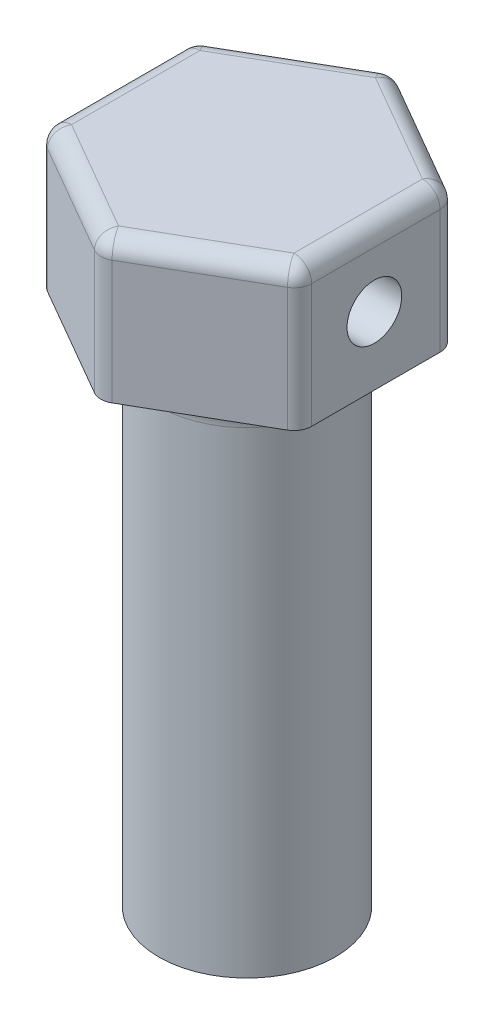
SolidWorks part; units mm, degrees
ref_plane "Front Plane" through (0, 0, 0) normal (0, 0, 1) x (1, 0, 0)
ref_plane "Top Plane" through (0, 0, 0) normal (0, 1, 0) x (1, 0, 0)
ref_plane "Right Plane" through (0, 0, 0) normal (1, 0, 0) x (0, 0, -1)
sketch "Sketch1" plane through (0, 0, 0) normal (0, 1, 0) x (1, 0, 0)
  line L1 (7.3, -4.2147) -> (7.3, 4.2147)
  line L2 (7.3, 4.2147) -> (0, 8.4293)
  line L3 (0, 8.4293) -> (-7.3, 4.2147)
  line L4 (-7.3, 4.2147) -> (-7.3, -4.2147)
  line L5 (-7.3, -4.2147) -> (0, -8.4293)
  line L6 (0, -8.4293) -> (7.3, -4.2147)
  circle A0 centre (0, 0) radius 7.3 construction
  dimension "D1" = 14.6
extrude "Boss-Extrude1" add sketch "Sketch1" along normal blind 8
sketch "Sketch2" plane through (0, 0, 0) normal (0, -1, 0) x (1, 0, 0)
  line L0 (-1.5, 1.4518) -> (-1.5, -1.4518)
  line L1 (-7.3, -4.2147) -> (-7.3, 4.2147) construction
  arc A0 (-1.5, -1.4518) -> (-1.5, 1.4518) centre (0, 0) ccw
  circle A1 centre (0, 0) radius 5
  dimension "D1" = 4.175
  dimension "D2" = 10
  dimension "D3" = 1.5
extrude "Boss-Extrude2" add sketch "Sketch2" along normal blind 29 contours A1 | A0 L0
fillet "Fillet1" radius 2 1 edges at (0, 0, 5)
sketch "Sketch3" plane through (7.3, 0, 0) normal (1, 0, 0) x (0, 0, -1)
  line L0 (-7, 0) -> (7, 0) construction
  line L1 (4.2147, 8) -> (4.2147, 0) construction
  circle A0 centre (-0.0853, 3.85) radius 1.55
  dimension "D1" = 3.1
  dimension "D2" = 3.85
  dimension "D3" = 4.3
extrude "Cut-Extrude1" cut sketch "Sketch3" against normal through all
fillet "Fillet2" radius 1 12 edges at (-3.65, 8, 6.322) (-7.3, 8, 0) (-3.65, 8, -6.322) (3.65, 8, -6.322) (7.3, 8, 0) (3.65, 8, 6.322) (-7.3, 4, -4.2147) (0, 4, -8.4293) (7.3, 4, -4.2147) (7.3, 4, 4.2147) (0, 4, 8.4293) (-7.3, 4, 4.2147)
sketch "Sketch4" plane through (0, 0, 0) normal (1, 0, 0) x (0, 0, -1)
  line L1 (-16.1086, 1.5942) -> (18.1695, 1.5942)
  line L2 (-16.1086, 1.5942) -> (-16.1086, -34.824)
  line L3 (-16.1086, -34.824) -> (18.1695, -34.824)
  line L4 (18.1695, 1.5942) -> (18.1695, -34.824)
extrude "Cut-Extrude2" [suppressed] cut sketch "Sketch4" against normal through all both and the other way through all
sketch "Sketch5" plane through (0, -29, 0) normal (0, -1, 0) x (1, 0, 0)
  circle A0 centre (0, 0) radius 2.0875
  dimension "D1" = 4.175
extrude "Cut-Extrude3" cut sketch "Sketch5" against normal blind 2
